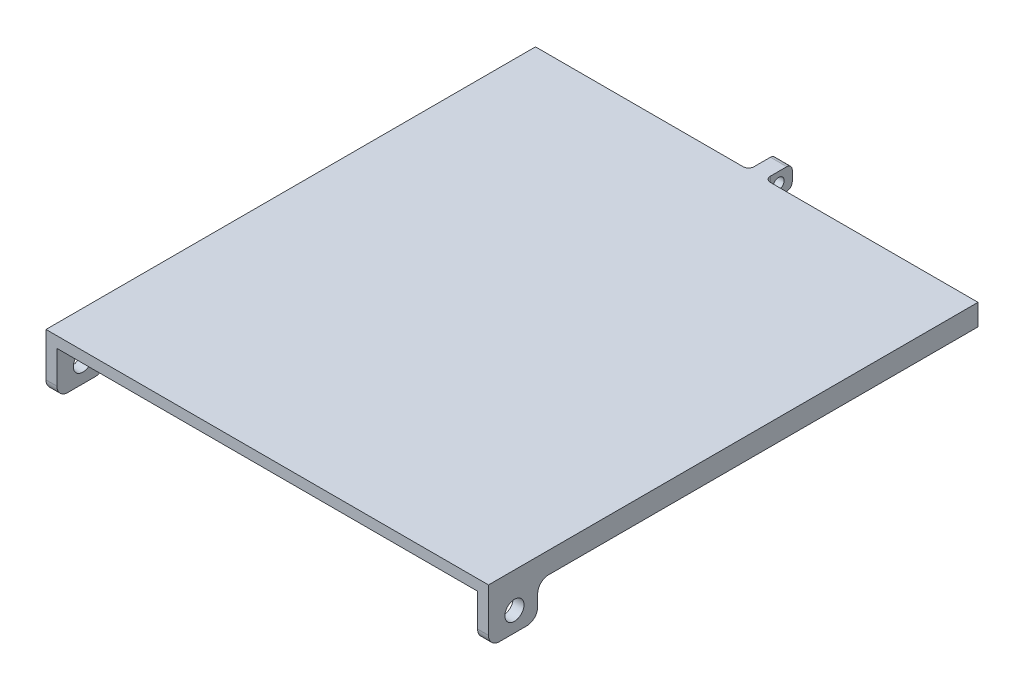
SolidWorks part; units mm, degrees
ref_plane "Front Plane" through (0, 0, 0) normal (0, 0, 1) x (1, 0, 0)
ref_plane "Top Plane" through (0, 0, 0) normal (0, 1, 0) x (1, 0, 0)
ref_plane "Right Plane" through (0, 0, 0) normal (1, 0, 0) x (0, 0, -1)
sketch "Sketch1" plane through (0, 0, 0) normal (0, 1, 0) x (1, 0, 0)
  line L0 (-46.1415, 4.4886) -> (-46.1415, 13.4886)
  line L2 (-46.1415, 13.4886) -> (-46.1415, 92.0886)
  line L3 (-46.1415, 92.0886) -> (30.8585, 92.0886)
  line L4 (30.8585, 92.0886) -> (30.8585, 13.4886)
  line L6 (30.8585, 13.4886) -> (30.8585, 4.4886)
  line L7 (30.8585, 4.4886) -> (32.8585, 4.4886)
  line L8 (32.8585, 4.4886) -> (32.8585, 94.0886)
  line L11 (32.8585, 94.0886) -> (-48.1415, 94.0886)
  line L13 (-48.1415, 94.0886) -> (-48.1415, 4.4886)
  line L14 (-48.1415, 4.4886) -> (-46.1415, 4.4886)
  dimension "D1" = 77
  dimension "D2" = 2
  dimension "D3" = 87.6
  dimension "D4" = 87.6
  dimension "D5" = 2
  dimension "D8" = 2
extrude "Boss-Extrude2" add sketch "Sketch1" along normal blind 8 contours L13 L14 L0 L2 L3 L4 L6 L7 L8 L11
sketch "Sketch2" plane through (0, 8, 0) normal (0, 1, 0) x (1, 0, 0)
  line L1 (-48.1415, 94.0886) -> (32.8585, 94.0886)
  line L2 (-48.1415, 94.0886) -> (-48.1415, 4.4886)
  line L3 (-48.1415, 4.4886) -> (32.8585, 4.4886)
  line L4 (32.8585, 94.0886) -> (32.8585, 4.4886)
  line L6 (32.8585, 4.4886) -> (32.8585, 94.0886) construction
  line L7 (30.8585, 4.4886) -> (32.8585, 4.4886) construction
  dimension "D1" = 0
  dimension "D2" = 0
extrude "Boss-Extrude3" add sketch "Sketch2" along normal blind 2
sketch "Sketch3" plane through (32.8585, 0, 0) normal (1, 0, 0) x (0, 0, -1)
  line L0 (4.4886, 10) -> (94.0886, 10) construction
  line L1 (4.4886, 10) -> (4.4886, 0) construction
  circle A0 centre (9.2386, 3.6) radius 1.75
  dimension "D1" = 3.5
  dimension "D2" = 6.4
  dimension "D3" = 4.75
extrude "Cut-Extrude1" cut sketch "Sketch3" against normal through all
sketch "Sketch4" plane through (30.8585, 0, 0) normal (-1, 0, 0) x (0, 0, 1)
  line L0 (-92.0886, 8) -> (-4.4886, 8) construction
  line L1 (-94.0886, 6.1) -> (-13.4886, 6.1)
  line L2 (-94.0886, 6.1) -> (-94.0886, 0)
  line L3 (-94.0886, 0) -> (-13.4886, 0)
  line L4 (-13.4886, 6.1) -> (-13.4886, 0)
  line L5 (-94.0886, 10) -> (-94.0886, 0) construction
  dimension "D1" = 1.9
  dimension "D2" = 0
extrude "Cut-Extrude2" cut sketch "Sketch4" against normal through all both and the other way through all
sketch "Sketch5" plane through (0, 8, 0) normal (0, -1, 0) x (1, 0, 0)
  line L0 (-46.1415, -4.4886) -> (-46.1415, -92.0886) construction
  line L1 (26.7585, -13.0053) -> (-42.0415, -13.0053)
  line L2 (26.7585, -13.0053) -> (26.7585, -11.8053)
  line L3 (26.7585, -11.8053) -> (-42.0415, -11.8053)
  line L4 (-42.0415, -13.0053) -> (-42.0415, -11.8053)
  line L5 (-42.6415, -13.5553) -> (27.3585, -13.5553) construction
  dimension "D1" = 1.2
  dimension "D2" = 68.8
  dimension "D3" = 4.1
  dimension "D4" = 0.55
extrude "Boss-Extrude4" add sketch "Sketch5" along normal blind 2
fillet "Fillet2" radius 2 7 edges at (-7.6415, 8, -11.8053) (-47.1415, 0, -4.4886) (-47.1415, 0, -13.4886) (-47.1415, 6.1, -13.4886) (31.8585, 6.1, -13.4886) (31.8585, 0, -4.4886) (31.8585, 0, -13.4886)
ref_plane "Plane1" through (-7.6415, 0, 0) normal (-1, 0, 0) x (0, 0, 1)
sketch "Sketch7" plane through (-7.6415, 0, 0) normal (-1, 0, 0) x (0, 0, 1)
  line L0 (-94.0886, 10) -> (-94.0886, 6.1) construction
  line L1 (-94.0886, 10) -> (-98.0886, 10)
  line L2 (-94.0886, 10) -> (-94.0886, 6.1)
  line L3 (-94.0886, 6.1) -> (-98.0886, 6.1)
  line L4 (-99.0886, 9) -> (-99.0886, 7.1)
  arc A0 (-99.0886, 7.1) -> (-98.0886, 6.1) centre (-98.0886, 7.1) ccw
  arc A1 (-99.0886, 9) -> (-98.0886, 10) centre (-98.0886, 9) cw
  circle A2 centre (-96.5886, 8.05) radius 1
  point P14 (-99.0886, 10)
  point P17 (-99.0886, 8.05)
  dimension "D2" = 1
  dimension "D3" = 2
  dimension "D4" = 1.95
  dimension "D5" = 2.5
  dimension "D1" = 5
extrude "Boss-Extrude5" add sketch "Sketch7" along normal blind 1.5 and the other way blind 1.5
fillet "Fillet5" radius 1 2 edges at (-6.1415, 8.05, -94.0886) (-9.1415, 8.05, -94.0886)
